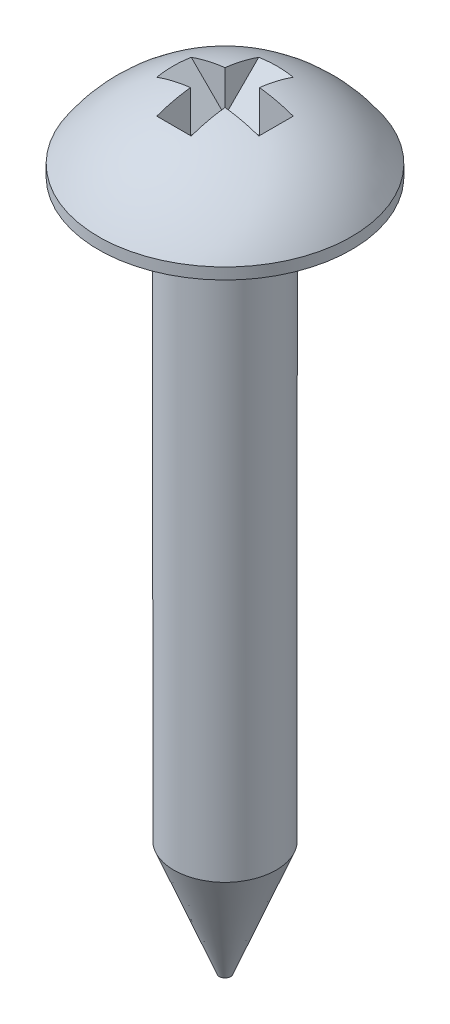
SolidWorks part; units mm, degrees
ref_plane "Front" through (0, 0, 0) normal (0, 0, 1) x (1, 0, 0)
ref_plane "Top" through (0, 0, 0) normal (0, 1, 0) x (1, 0, 0)
ref_plane "Right" through (0, 0, 0) normal (1, 0, 0) x (0, 0, -1)
ref_axis "side-side" through (80.9, 0, 0) along (-1, 0, 0)
ref_axis "up-down" through (0, 50, 0) along (0, -1, 0)
ref_axis "front-back" through (0, 0, -80.9) along (0, 0, 1)
sketch "Sketch1" plane through (0, 0, 0) normal (0, 0, 1) x (1, 0, 0)
  line L0 (0, 0) -> (0, 5.7251) construction
  line L1 (2.794, 0.25) -> (2.794, 0)
  line L2 (0.125, -15.24) -> (1.13, -12.7)
  line L3 (0, 1.75) -> (0, -15.24)
  line L4 (0, -15.24) -> (0.125, -15.24)
  line L5 (1.13, 0) -> (1.13, -12.7)
  line L6 (1.13, 0) -> (2.794, 0)
  arc A0 (0, 1.75) -> (2.794, 0.25) centre (0, -1.6021) cw
  dimension "D1" = 0.25
  dimension "D2" = 2.26
  dimension "D3" = 1.75
  dimension "D4" = 5.588
  dimension "D5" = 15.24
  dimension "D6" = 0.25
  dimension "D7" = 2.54
revolve "Revolve1" add sketch "Sketch1" angle 360 about L0
sketch "Sketch2" plane through (0, 0, 0) normal (0, 0, 1) x (1, 0, 0)
  line L0 (-1.8, 2.2061) -> (-0.381, 0.7871)
  line L1 (0.381, 0.7871) -> (1.8, 2.2061)
  line L2 (1.8, 2.2061) -> (-1.8, 2.2061)
  line L3 (-0.381, 0.7871) -> (0.381, 0.7871)
  line L4 (0, 0.4061) -> (0, 3.624) construction
  arc A0 (2.794, 0.25) -> (-2.794, 0.25) centre (0, -1.6021) ccw construction
  point P3 (-1.143, 1.5491)
  dimension "D1" = 2.286
  dimension "D2" = 1.8
  dimension "D3" = 0.762
extrude "Cut-Extrude1" cut sketch "Sketch2" against normal mid plane 0.762
pattern_circular "CirPattern1" count 2 over 90 about axis through (0, 50, 0) along (0, -1, 0) of "Cut-Extrude1"
